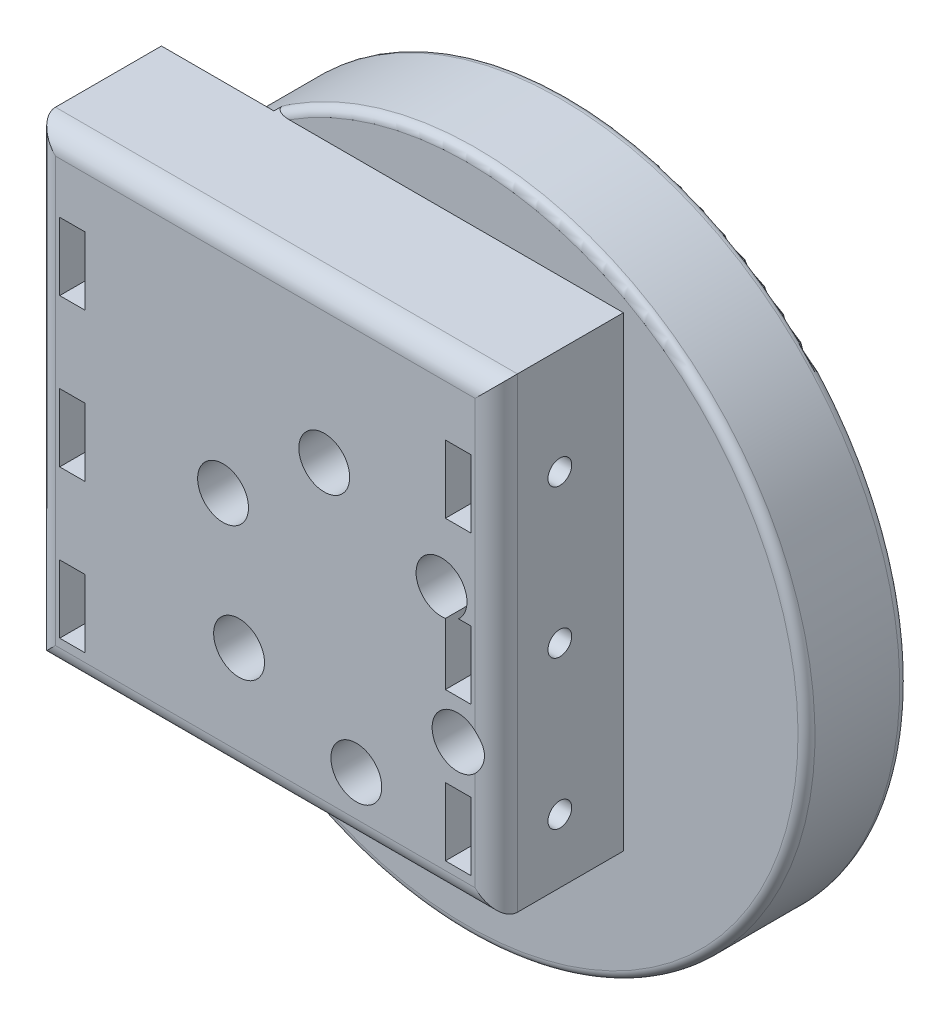
SolidWorks part; units mm, degrees
ref_plane "Front Plane" through (0, 0, 0) normal (0, 0, 1) x (1, 0, 0)
ref_plane "Top Plane" through (0, 0, 0) normal (0, 1, 0) x (1, 0, 0)
ref_plane "Right Plane" through (0, 0, 0) normal (1, 0, 0) x (0, 0, -1)
sketch "Sketch1" plane through (0, 0, 0) normal (0, 0, 1) x (1, 0, 0)
  line L0 (0, 34.9793) -> (0, -39.688) construction
  line L2 (-27.25, 37.5) -> (27.25, 37.5)
  line L3 (-27.25, 37.5) -> (-27.25, -17.5)
  line L4 (-27.25, -17.5) -> (27.25, -17.5)
  line L5 (27.25, 37.5) -> (27.25, -17.5)
  line L6 (-27.25, 37.5) -> (27.25, -17.5) construction
  line L7 (-27.25, -17.5) -> (27.25, 37.5) construction
  point P3 (0, 10)
  dimension "D1" = 10
  dimension "D2" = 54.5
  dimension "D3" = 55
extrude "Boss-Extrude1" add sketch "Sketch1" along normal blind 15
sketch "Sketch4" plane through (-27.25, 0, 0) normal (-1, 0, 0) x (0, 0, 1)
  line L0 (7.5, 37.5) -> (7.5, -17.5) construction
  line L1 (15, 37.5) -> (15, -17.5) construction
  line L5 (15, -17.5) -> (0, -17.5) construction
  line L7 (15, 37.5) -> (0, 37.5) construction
  circle A0 centre (7.5, 25) radius 1.4
  circle A1 centre (7.5, -10) radius 1.4
  circle A2 centre (7.5, 7.5) radius 1.4
  dimension "D2" = 2.8
  dimension "D3" = 2.8
  dimension "D4" = 17.5
  dimension "D5" = 2.8
  dimension "D1" = 17.5
  dimension "D6" = 25
extrude "Cut-Extrude2" cut sketch "Sketch4" against normal through all
sketch "Sketch10" plane through (0, 0, 0) normal (0, 0, -1) x (-1, 0, 0)
  line L0 (-27.25, -17.5) -> (-27.25, 37.5) construction
  circle A0 centre (-8.85, 4.6559) radius 40
  dimension "D1" = 80
  dimension "D2" = 10
  dimension "D3" = 18.4
extrude "Boss-Extrude5" add sketch "Sketch10" along normal blind 12
sketch "Sketch11" plane through (0, 0, -12) normal (0, 0, -1) x (-1, 0, 0)
  circle A0 centre (-8.85, 4.6559) radius 25.15
  circle A1 centre (-8.85, 4.6559) radius 40 construction
  dimension "D1" = 0
  dimension "D2" = 50.3
extrude "Cut-Extrude3" cut sketch "Sketch11" against normal blind 7
sketch "Sketch12" plane through (0, 0, -5) normal (0, 0, -1) x (-1, 0, 0)
  circle A0 centre (-6.9591, 19.5363) radius 1.6
  circle A1 centre (-8.85, 4.6559) radius 25.15 construction
  circle A2 centre (4.9822, 10.4585) radius 1.6
  circle A3 centre (3.0913, -4.4218) radius 1.6
  circle A4 centre (-10.7409, -10.2244) radius 1.6
  circle A5 centre (-22.6822, -1.1467) radius 1.6
  circle A6 centre (-20.7913, 13.7336) radius 1.6
  point P17 (-8.85, 4.6559)
  point P18 (-8.85, 4.6559)
  point P19 (-8.85, 4.6559)
  point P20 (-8.85, 4.6559)
  point P21 (-8.85, 4.6559)
  point P22 (-8.85, 4.6559)
  dimension "D1" = 3.2
  dimension "D2" = 15
  dimension "D3" = 6
extrude "Cut-Extrude4" cut sketch "Sketch12" against normal through all
sketch "Sketch13" plane through (0, 0, 15) normal (0, 0, 1) x (1, 0, 0)
  circle A0 centre (10.7409, -10.2244) radius 3
  circle A1 centre (-3.0913, -4.4218) radius 3
  circle A2 centre (-4.9822, 10.4585) radius 3
  circle A3 centre (6.9591, 19.5363) radius 3
  circle A4 centre (20.7913, 13.7336) radius 3
  circle A5 centre (22.6822, -1.1467) radius 3
  point P15 (8.85, 4.6559)
  dimension "D1" = 6
  dimension "D2" = 6
extrude "Cut-Extrude5" cut sketch "Sketch13" against normal blind 15
fillet "Fillet5" radius 2.5 4 edges at (-27.25, 10, 15) (0, -17.5, 15) (27.25, 10, 15) (0, 37.5, 15)
fillet "Fillet6" radius 1 1 edges at (-16.3, 4.6559, -12)
fillet "Fillet7" radius 1 1 edges at (48.1441, -2.8258, 0)
fillet "Fillet8" radius 1 1 edges at (-31.15, 4.6559, 0)
fillet "Fillet9" radius 1 1 edges at (-31.15, 4.6559, -12)
sketch "Sketch16" plane through (0, 0, 15) normal (0, 0, 1) x (1, 0, 0)
  line L0 (-24.75, 7.5) -> (24.75, 7.5) construction
  line L1 (-24.75, 35) -> (-24.75, -15) construction
  line L2 (24.75, 1.0268) -> (24.75, 35) construction
  line L3 (27.25, -17.5) -> (27.25, 37.5) construction
  line L4 (-23.2454, -17.5) -> (27.25, -17.5) construction
  line L5 (-24.75, -10) -> (24.75, -10) construction
  line L6 (24.75, -15) -> (24.75, -3.3202) construction
  line L7 (-24.75, 25) -> (24.75, 25) construction
  line L8 (-27.25, -17.5) -> (-27.25, 37.5) construction
  line L9 (-24.25, 21) -> (-21.25, 21)
  line L10 (-24.25, 21) -> (-24.25, 29)
  line L11 (-24.25, 29) -> (-21.25, 29)
  line L12 (-21.25, 21) -> (-21.25, 29)
  line L13 (-24.25, 21) -> (-21.25, 29) construction
  line L14 (-24.25, 29) -> (-21.25, 21) construction
  line L15 (21.25, 21) -> (24.25, 21)
  line L16 (21.25, 21) -> (21.25, 29)
  line L17 (21.25, 29) -> (24.25, 29)
  line L18 (24.25, 21) -> (24.25, 29)
  line L19 (21.25, 21) -> (24.25, 29) construction
  line L20 (21.25, 29) -> (24.25, 21) construction
  line L21 (21.25, 3.5) -> (24.25, 3.5)
  line L22 (21.25, 3.5) -> (21.25, 11.5)
  line L23 (21.25, 11.5) -> (24.25, 11.5)
  line L24 (24.25, 3.5) -> (24.25, 11.5)
  line L25 (21.25, 3.5) -> (24.25, 11.5) construction
  line L26 (21.25, 11.5) -> (24.25, 3.5) construction
  line L27 (-24.25, 3.5) -> (-21.25, 3.5)
  line L28 (-24.25, 3.5) -> (-24.25, 11.5)
  line L29 (-24.25, 11.5) -> (-21.25, 11.5)
  line L30 (-21.25, 3.5) -> (-21.25, 11.5)
  line L31 (-24.25, 3.5) -> (-21.25, 11.5) construction
  line L32 (-24.25, 11.5) -> (-21.25, 3.5) construction
  line L33 (21.25, -14) -> (24.25, -14)
  line L34 (21.25, -14) -> (21.25, -6)
  line L35 (21.25, -6) -> (24.25, -6)
  line L36 (24.25, -14) -> (24.25, -6)
  line L37 (21.25, -14) -> (24.25, -6) construction
  line L38 (21.25, -6) -> (24.25, -14) construction
  line L39 (-24.25, -14) -> (-21.25, -14)
  line L40 (-24.25, -14) -> (-24.25, -6)
  line L41 (-24.25, -6) -> (-21.25, -6)
  line L42 (-21.25, -14) -> (-21.25, -6)
  line L43 (-24.25, -14) -> (-21.25, -6) construction
  line L44 (-24.25, -6) -> (-21.25, -14) construction
  point P14 (-22.75, 25)
  point P21 (22.75, 25)
  point P28 (-22.75, 7.5)
  point P34 (22.75, 7.5)
  point P39 (-22.75, -10)
  point P44 (22.75, -10)
  dimension "D1" = 25
  dimension "D2" = 17.5
  dimension "D3" = 17.5
  dimension "D4" = 4.5
  dimension "D5" = 8
  dimension "D6" = 3
  dimension "D7" = 8
  dimension "D8" = 3
  dimension "D9" = 4.5
  dimension "D10" = 3
extrude "Cut-Extrude6" cut sketch "Sketch16" against normal blind 10
